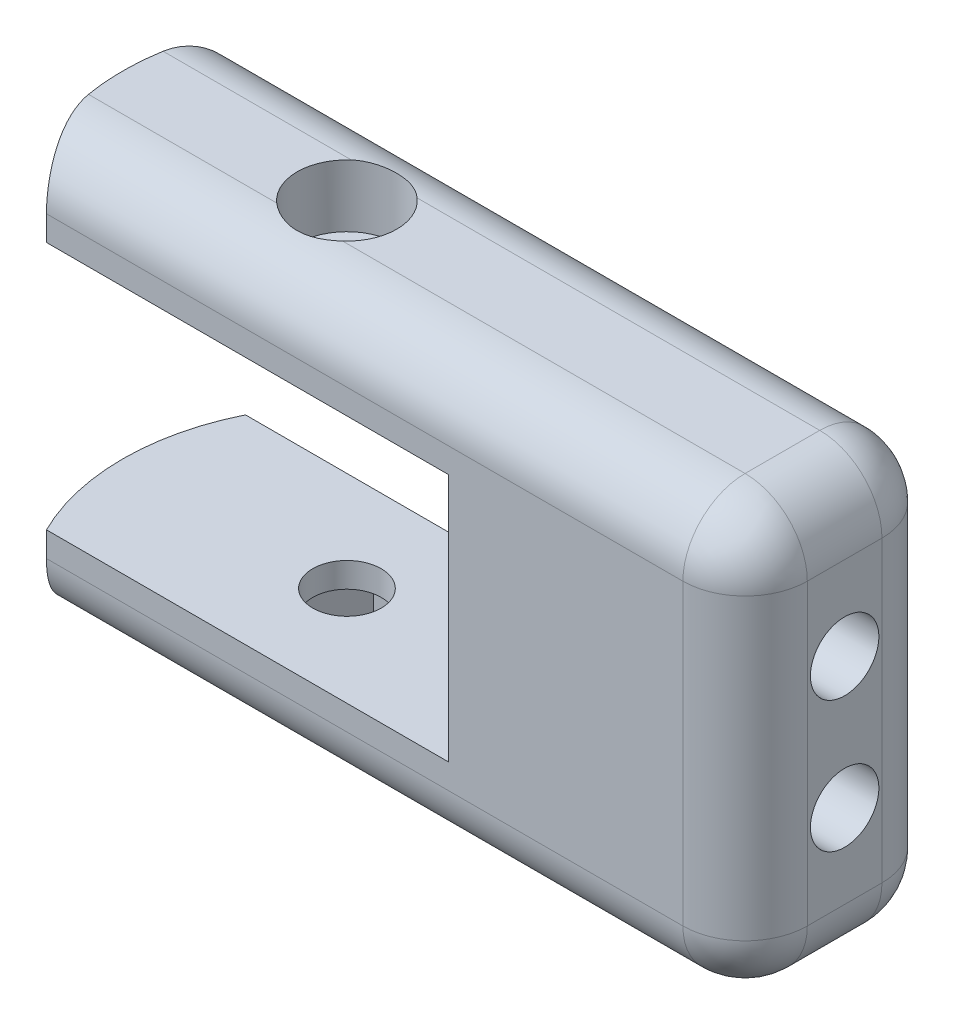
SolidWorks part; units mm, degrees
ref_plane "Plan de face" through (0, 0, 0) normal (0, 0, 1) x (1, 0, 0)
ref_plane "Plan de dessus" through (0, 0, 0) normal (0, 1, 0) x (1, 0, 0)
ref_plane "Plan de droite" through (0, 0, 0) normal (1, 0, 0) x (0, 0, -1)
sketch "Esquisse1" plane through (0, 0, 0) normal (0, 0, 1) x (1, 0, 0)
  line L1 (0, 0) -> (50, 0)
  line L2 (0, 0) -> (0, 34)
  line L3 (0, 34) -> (50, 34)
  line L4 (50, 0) -> (50, 34)
  dimension "D1" = 34
  dimension "D2" = 50
extrude "Boss.-Extru.1" add sketch "Esquisse1" along normal blind 30
sketch "Esquisse3" plane through (0, 34, 0) normal (0, 1, 0) x (1, 0, 0)
  line L0 (0, 0) -> (20, -30) construction
  line L1 (50, -30) -> (0, -30) construction
  line L2 (20, -30) -> (0, -30) construction
  line L7 (50, 0) -> (0, 0)
  line L8 (0, 0) -> (0, -30)
  line L9 (0, -30) -> (50, -30)
  line L10 (50, -30) -> (50, 0)
  line L12 (0, 0) -> (0, -30)
  arc A0 (0, 0) -> (0, -30) centre (10, -15) ccw
  point P3 (10, -15)
  dimension "D1" = 20
extrude "Boss.-Extru.2" add sketch "Esquisse3" against normal blind 7
ref_plane "Plan1" through (0, 17, 0) normal (0, 1, 0) x (1, 0, 0)
mirror "Symétrie1" about plane through (0, 17, 0) normal (0, 1, 0) of "Boss.-Extru.2"
sketch "Esquisse4" plane through (0, 34, 0) normal (0, 1, 0) x (1, 0, 0)
  line L0 (0, 0) -> (20, -30) construction
  line L1 (50, -30) -> (0, -30) construction
  line L2 (20, -30) -> (0, -30) construction
  circle A0 centre (10, -15) radius 4
  dimension "D1" = 20
  dimension "D2" = 8
extrude "Enlèv. mat.-Extru.1" cut sketch "Esquisse4" against normal blind 5
sketch "Esquisse5" plane through (0, 29, 0) normal (0, 1, 0) x (1, 0, 0)
  circle A0 centre (10, -15) radius 2.75
  dimension "D1" = 5.5
extrude "Enlèv. mat.-Extru.2" cut sketch "Esquisse5" against normal through all
sketch "Esquisse6" plane through (0, 0, 0) normal (0, -1, 0) x (1, 0, 0)
  line L0 (0, 0) -> (50, 0) construction
  line L1 (7.1132, 20) -> (4.2265, 15)
  line L2 (4.2265, 15) -> (7.1132, 10)
  line L3 (7.1132, 10) -> (12.8868, 10)
  line L4 (12.8868, 10) -> (15.7735, 15)
  line L5 (15.7735, 15) -> (12.8868, 20)
  line L6 (12.8868, 20) -> (7.1132, 20)
  circle A0 centre (10, 15) radius 5 construction
  dimension "D1" = 10
extrude "Enlèv. mat.-Extru.3" cut sketch "Esquisse6" against normal blind 5
sketch "Esquisse7" plane through (0, 0, 0) normal (-1, 0, 0) x (0, 0, 1)
  line L0 (15, 7) -> (15, 11.7267) construction
  line L3 (30, 7) -> (0, 7) construction
  line L4 (15, 11.7267) -> (15, 22.2733) construction
  line L5 (15, 22.2733) -> (15, 27) construction
  line L6 (30, 27) -> (0, 27) construction
  circle A0 centre (15, 11.7267) radius 2.75
  circle A1 centre (15, 22.2733) radius 2.75
  dimension "D1" = 5.5
extrude "Enlèv. mat.-Extru.4" cut sketch "Esquisse7" against normal through all
sketch "Esquisse8" plane through (0, 0, 0) normal (-1, 0, 0) x (0, 0, 1)
  circle A0 centre (15, 11.7267) radius 4.5
  circle A1 centre (15, 22.2733) radius 4.5
  dimension "D1" = 9
extrude "Enlèv. mat.-Extru.5" cut sketch "Esquisse8" against normal blind 45
sketch "Esquisse9" plane through (0, 0, 0) normal (0, 0, -1) x (-1, 0, 0)
  line L1 (0, 7) -> (-20, 7)
  line L2 (0, 7) -> (0, 27)
  line L3 (0, 27) -> (-20, 27)
  line L4 (-20, 7) -> (-20, 27)
  dimension "D1" = 20
extrude "Enlèv. mat.-Extru.6" cut sketch "Esquisse9" against normal through all
sketch "Esquisse11" plane through (0, 7, 0) normal (0, 1, 0) x (1, 0, 0)
  circle A0 centre (10, -15) radius 18.0278
extrude "Enlèv. mat.-Extru.7" cut sketch "Esquisse11" along normal up to surface (20 mm away) up to face at (7.9931, 27, 15)
sketch "Esquisse12" plane through (50, 0, 0) normal (1, 0, 0) x (0, 0, -1)
  line L0 (-30, 0) -> (0, 0) construction
  line L1 (0, 34) -> (-7, 34)
  line L2 (0, 34) -> (0, 0)
  line L3 (0, 0) -> (-7, 0)
  line L4 (-7, 34) -> (-7, 0)
  line L6 (-30, 34) -> (-23, 34)
  line L7 (-30, 34) -> (-30, 0)
  line L8 (-30, 0) -> (-23, 0)
  line L9 (-23, 34) -> (-23, 0)
  dimension "D1" = 7
extrude "Enlèv. mat.-Extru.8" cut sketch "Esquisse12" against normal through all
fillet "Congé1" radius 5 8 edges at (50, 0, 15) (50, 17, 7) (50, 34, 15) (50, 17, 23) (21.9223, 34, 7) (21.9223, 34, 23) (21.9223, 0, 23) (21.9223, 0, 7)
